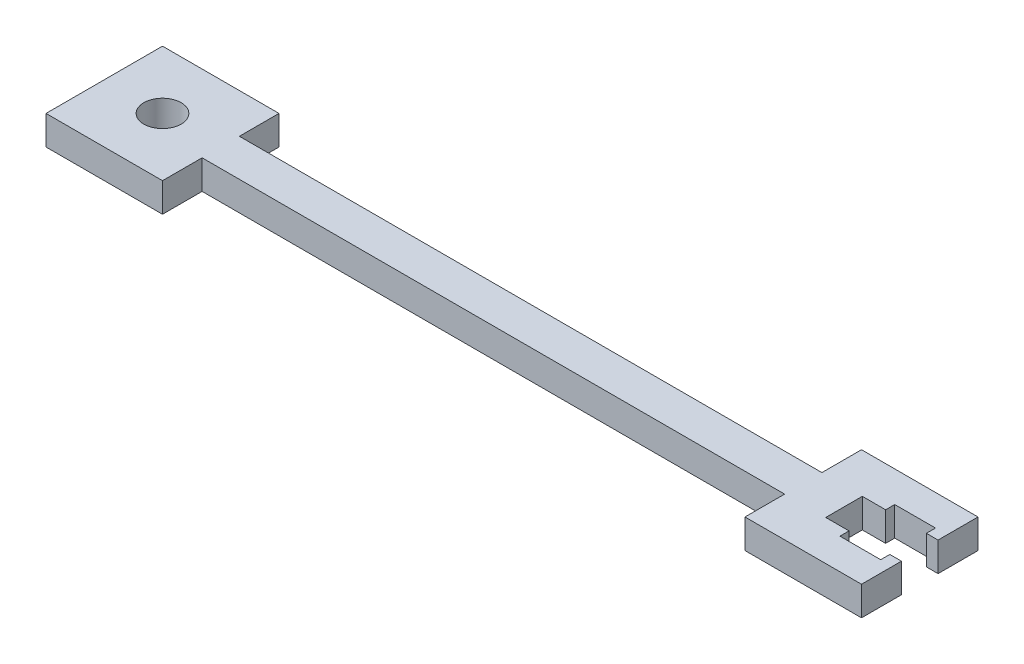
SolidWorks part; units mm, degrees
ref_plane "Front Plane" through (0, 0, 0) normal (0, 0, 1) x (1, 0, 0)
ref_plane "Top Plane" through (0, 0, 0) normal (0, 1, 0) x (1, 0, 0)
ref_plane "Right Plane" through (0, 0, 0) normal (1, 0, 0) x (0, 0, -1)
sketch "Sketch1" plane through (0, 0, 0) normal (0, 1, 0) x (1, 0, 0)
  line L0 (0, 20) -> (0, -20) construction
  line L1 (20, 6.4) -> (220, 6.4)
  line L2 (20, -6.4) -> (20, -20)
  line L3 (20, -6.4) -> (220, -6.4)
  line L4 (220, 6.4) -> (220, 20)
  line L5 (220, -20) -> (260, -20)
  line L6 (220, -20) -> (220, -6.4)
  line L7 (220, 20) -> (260, 20)
  line L8 (260, -20) -> (260, -6.285)
  line L9 (-20, 20) -> (20, 20)
  line L10 (-20, 20) -> (-20, -20)
  line L11 (-20, -20) -> (20, -20)
  line L12 (20, 20) -> (20, 6.4)
  line L13 (260, 6.285) -> (260, 20)
  line L14 (-20, 0) -> (20, 0) construction
  line L15 (20, 0) -> (-20, 0) construction
  line L16 (260, 6.285) -> (256, 6.285)
  line L17 (242, 6.285) -> (234, 6.285)
  line L18 (260, -6.285) -> (256, -6.285)
  line L19 (234, 6.285) -> (234, -6.285)
  line L20 (242, 9.41) -> (256, 9.41)
  line L21 (242, 9.41) -> (242, 6.285)
  line L22 (242, -9.41) -> (256, -9.41)
  line L23 (256, 9.41) -> (256, 6.285)
  line L24 (256, -6.285) -> (256, -9.41)
  line L25 (242, -6.285) -> (242, -9.41)
  line L26 (249, 9.41) -> (249, -9.41) construction
  line L28 (242, -6.285) -> (234, -6.285)
  circle A0 centre (0, 0) radius 6.4
  point P20 (220, 0)
  point P28 (234, 0)
  point P29 (246, 0)
  point P36 (249, 0)
  dimension "D4" = 12.8
  dimension "D1" = 280
  dimension "D2" = 40
  dimension "D3" = 40
  dimension "D5" = 40
  dimension "D6" = 40
  dimension "D7" = 12.8
  dimension "D8" = 13.6
  dimension "D9" = 13.6
  dimension "D10" = 12.57
  dimension "D11" = 18.82
  dimension "D12" = 26
  dimension "D13" = 8
  dimension "D14" = 4
extrude "Boss-Extrude1" add sketch "Sketch1" along normal blind 10
equation "\"D5@Sketch1\"=\"D2@Sketch1\""
equation "\"D3@Sketch1\"=\"D2@Sketch1\""
equation "\"D6@Sketch1\"=\"D2@Sketch1\""
equation "\"D7@Sketch1\"=\"D4@Sketch1\""
